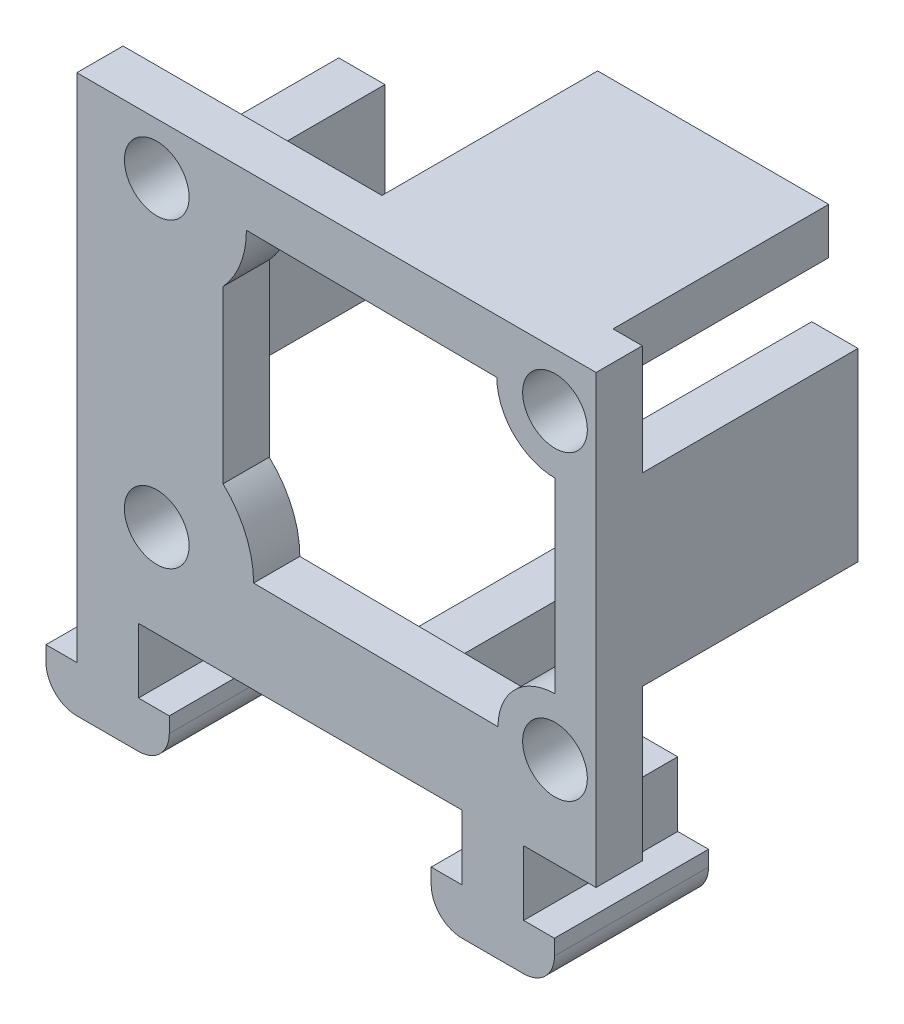
SolidWorks part; units mm, degrees
ref_plane "Спереди" through (0, 0, 0) normal (0, 0, 1) x (1, 0, 0)
ref_plane "Сверху" through (0, 0, 0) normal (0, 1, 0) x (1, 0, 0)
ref_plane "Справа" through (0, 0, 0) normal (1, 0, 0) x (0, 0, -1)
sketch "Эскиз2" plane through (0, 0, 0) normal (0, 0, 1) x (1, 0, 0)
  line L0 (-9.4906, 0) -> (-9.4906, -2.25)
  line L1 (24.2094, 26.7) -> (-9.4906, 26.7)
  line L2 (24.2094, 26.7) -> (24.2094, 0)
  line L4 (-9.4906, 26.7) -> (-9.4906, 0)
  line L5 (-9.4906, -2.25) -> (24.2094, -2.25)
  line L6 (24.2094, -2.25) -> (24.2094, 0)
  line L7 (24.2094, 26.7) -> (30.9983, 26.7) construction
  line L8 (-4.3039, 23.3473) -> (-4.3401, 26.7) construction
  line L9 (-4.3039, 23.3473) -> (-9.4906, 23.3473) construction
  line L10 (0, 19.4273) -> (0, 8.3348)
  line L11 (21.5439, 19.4273) -> (21.5439, 7.303)
  line L12 (1.9845, 3.75) -> (17.8424, 3.6015)
  line L13 (-9.4906, 26.7) -> (-4.3401, 26.7) construction
  line L14 (17.7698, 23.2014) -> (1.5175, 23.3473)
  circle A0 centre (21.5439, 3.6015) radius 2.1
  circle A1 centre (21.5439, 23.2014) radius 2.1
  circle A2 centre (-4.3039, 23.3473) radius 2.1
  circle A3 centre (-4.3039, 3.75) radius 2.1
  arc A4 (21.5439, 7.303) -> (17.8424, 3.6015) centre (21.5439, 3.6015) ccw
  arc A5 (17.7698, 23.2014) -> (21.5439, 19.4273) centre (21.5439, 23.2014) ccw
  arc A6 (0, 19.4273) -> (1.5175, 23.3473) centre (-4.3039, 23.3473) ccw
  arc A7 (1.9845, 3.75) -> (0, 8.3348) centre (-4.3039, 3.75) ccw
  point P12 (30.9983, 21.5985)
  point P13 (30.9983, 4.9988)
  point P14 (30.9983, 1.9985)
  point P15 (30.9983, 24.5985)
  point P16 (32.4984, 3.4986)
  point P25 (5.1505, 21.4035)
  point P26 (5.1505, 24.4965)
  dimension "D1" = 26.7
  dimension "D3" = 4.2
  dimension "D4" = 4.2
  dimension "D5" = 4.2
  dimension "D6" = 4.2
  dimension "D2" = 33.7
  dimension "D7" = 3.3529
  dimension "D8" = 5.1866
extrude "Бобышка-Вытянуть1" add sketch "Эскиз2" along normal blind 2 and the other way blind 1
sketch "Эскиз10" plane through (0, 0, -1) normal (0, 0, -1) x (-1, 0, 0)
  line L0 (-24.2094, 0.75) -> (-22.3105, 0.75) construction
  line L1 (-22.3105, 0.75) -> (-22.3105, 23.7) construction
  line L2 (6.4906, 3.3527) -> (-7.3105, 3.3527) construction
  line L3 (-7.3105, 3.3527) -> (-7.3105, 23.7) construction
  line L9 (-24.2094, 26.7) -> (9.4906, 26.7) construction
  line L10 (-22.3105, 23.7) -> (-7.3105, 23.7)
  line L11 (-22.3105, 23.7) -> (-22.3105, 26.7)
  line L12 (-22.3105, 26.7) -> (-7.3105, 26.7)
  line L13 (-7.3105, 23.7) -> (-7.3105, 26.7)
  line L14 (-24.2094, 0.75) -> (-24.2094, 7.5529) construction
  line L15 (-24.2094, 23.0985) -> (-24.2094, 19.5529) construction
  line L17 (-24.2094, 7.5529) -> (-21.2094, 7.5529)
  line L18 (-24.2094, 7.5529) -> (-24.2094, 19.5529)
  line L19 (-24.2094, 19.5529) -> (-21.2094, 19.5529)
  line L20 (-21.2094, 7.5529) -> (-21.2094, 19.5529)
  line L21 (6.4906, 7.5529) -> (6.4906, 19.0325) construction
  line L22 (9.4906, 26.7) -> (9.4906, -2.25) construction
  line L23 (6.4906, 7.5529) -> (9.4906, 7.5529)
  line L24 (6.4906, 7.5529) -> (6.4906, 19.0325)
  line L25 (6.4906, 19.0325) -> (9.4906, 19.0325)
  line L26 (9.4906, 7.5529) -> (9.4906, 19.0325)
  line L27 (-24.2094, -2.25) -> (-24.2094, 26.7) construction
  dimension "D1" = 15
  dimension "D2" = 12
  dimension "D3" = 3
  dimension "D4" = 3
  dimension "D6" = 3
extrude "Бобышка-Вытянуть4" add sketch "Эскиз10" along normal blind 14
sketch "Sketch1" plane through (0, 0, 2) normal (0, 0, 1) x (1, 0, 0)
  line L0 (-5.4906, -6.45) -> (-3.4906, -6.45)
  line L1 (-9.4906, -2.25) -> (-5.4906, -2.25)
  line L2 (-9.4906, -2.25) -> (-9.4906, -6.45)
  line L3 (-9.4906, -6.45) -> (-5.4906, -6.45)
  line L4 (-5.4906, -2.25) -> (-5.4906, -6.45)
  line L5 (-3.4906, -6.45) -> (-3.4906, -7.45)
  line L6 (-5.4906, -9.45) -> (-9.4906, -9.45)
  line L7 (-7.4906, -2.25) -> (-7.4906, -9.45) construction
  line L8 (-9.4906, -6.45) -> (-11.4906, -6.45)
  line L9 (-11.4906, -6.45) -> (-11.4906, -7.45)
  arc A0 (-3.4906, -7.45) -> (-5.4906, -9.45) centre (-5.4906, -7.45) cw
  arc A1 (-11.4906, -7.45) -> (-9.4906, -9.45) centre (-9.4906, -7.45) ccw
  point P11 (-3.4906, -9.45)
  line M12 (-9.4906, -2.25) -> (24.2094, -2.25)
  dimension "D5" = 2
  dimension "D1" = 4
  dimension "D2" = 4.2
  dimension "D3" = 3
  dimension "D4" = 4
extrude "Boss-Extrude1" add sketch "Sketch1" against normal blind 10 contours L7 L3 L8 L9 A1 L6 | L3 L7 L6 A0 L5 L0 | L1 L7 L3 L4 | L7 L2 L3 M12 region at (-5.6102, -7.8689, 2) region at (-6.4906, -4.35, 2) region at (-9.3709, -7.8689, 2) region at (-8.4906, -4.35, 2)
pattern_linear "LPattern1" count 2 spacing 25 along (1, 0, 0) of "Boss-Extrude1"
sketch "Sketch2" plane through (0, 0, -1) normal (0, 0, -1) x (-1, 0, 0)
  line L0 (5.4906, -2.25) -> (-15.5094, -2.25) construction
  line L1 (-10.7836, -2.25) -> (-7.7836, -2.25)
  line L2 (-10.7836, -2.25) -> (-10.7836, 1.75)
  line L3 (-10.7836, 1.75) -> (-7.7836, 1.75)
  line L4 (-7.7836, -2.25) -> (-7.7836, 1.75)
  dimension "D1" = 4
  dimension "D2" = 3
extrude "Boss-Extrude2" add sketch "Sketch2" along normal blind 14 contours L2 L3 L4 L1
sketch "Sketch3" plane through (15.5094, 0, 0) normal (-1, 0, 0) x (0, 0, 1)
  line L0 (-4.5, -2.25) -> (-1, -2.25)
  line L1 (-8, -2.25) -> (-1, -2.25) construction
  line L2 (-1, -2.25) -> (-1, 0.5589)
  line L3 (-1, 0.5589) -> (-4.5, -2.25)
extrude "Boss-Extrude3" add sketch "Sketch3" against normal blind 4
pattern_linear "LPattern2" count 2 spacing 25 along (-1, 0, 0) of "Boss-Extrude3"
